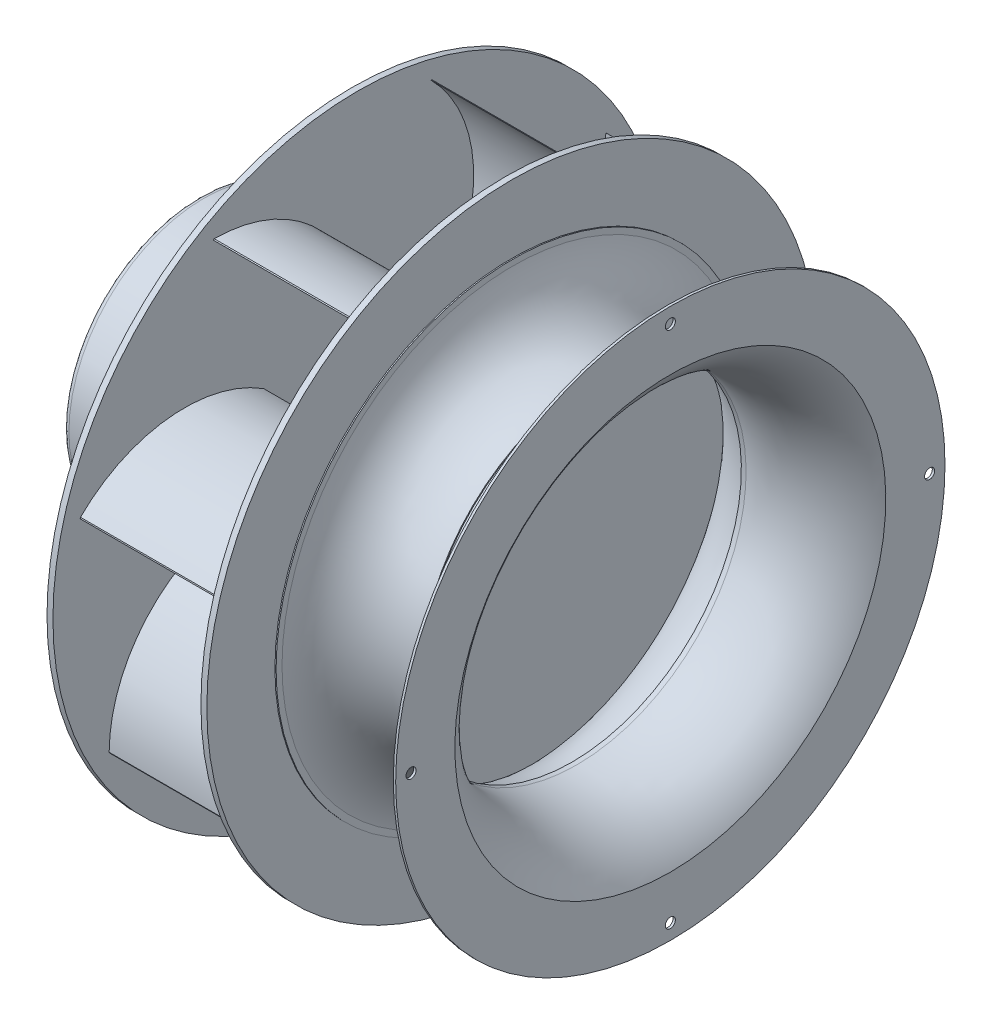
SolidWorks part; units mm, degrees
ref_plane "Front Plane" through (0, 0, 0) normal (0, 0, 1) x (1, 0, 0)
ref_plane "Top Plane" through (0, 0, 0) normal (0, 1, 0) x (1, 0, 0)
ref_plane "Right Plane" through (0, 0, 0) normal (1, 0, 0) x (0, 0, -1)
sketch "Sketch1" plane through (0, 0, 0) normal (0, 0, 1) x (1, 0, 0)
  line L0 (0, 0) -> (831.9083, 0) construction
  line L1 (0, 0) -> (0, 109)
  line L2 (5, 114) -> (70, 114)
  line L3 (70, 114) -> (70, 138)
  line L4 (70, 138) -> (90, 138)
  line L5 (90, 138) -> (90, 98)
  line L6 (90, 98) -> (95, 98)
  line L7 (95, 98) -> (95, 133)
  line L8 (95, 133) -> (105, 133)
  line L9 (105, 133) -> (105, 98)
  line L10 (105, 98) -> (130, 98)
  line L11 (130, 98) -> (130, 0)
  line L12 (130, 0) -> (0, 0)
  arc A0 (5, 114) -> (0, 109) centre (5, 109) ccw
  point P16 (0, 114)
  dimension "D10" = 5
  dimension "D1" = 114
  dimension "D2" = 24
  dimension "D3" = 70
  dimension "D4" = 40
  dimension "D5" = 35
  dimension "D6" = 5
  dimension "D7" = 20
  dimension "D8" = 10
  dimension "D9" = 60
revolve "Revolve1" add sketch "Sketch1" angle 360 about L0
sketch "Sketch2" plane through (130, 0, 0) normal (1, 0, 0) x (0, 0, -1)
  circle A0 centre (0, 0) radius 257.5
  dimension "D1" = 515
extrude "Extrude1" add sketch "Sketch2" along normal blind 5
sketch "Sketch9" plane through (130, 0, 0) normal (-1, 0, 0) x (0, 0, 1)
  circle A0 centre (0, 0) radius 252.5
  circle A1 centre (0, 0) radius 100
  circle A2 centre (0, 0) radius 257.5 construction
  dimension "D1" = 5
  dimension "D2" = 200
extrude "Extrude7" cut sketch "Sketch9" against normal blind 3
ref_plane "Plane1" through (260, 0, 0) normal (1, 0, 0) x (0, 0, -1)
sketch "Sketch3" plane through (260, 0, 0) normal (1, 0, 0) x (0, 0, -1)
  circle A0 centre (0, 0) radius 257.5
  dimension "D1" = 515
extrude "Extrude2" add sketch "Sketch3" along normal blind 5 separate body
sketch "Sketch4" plane through (135, 0, 0) normal (1, 0, 0) x (0, 0, -1)
  line L0 (0, 0) -> (0, 242.5) construction
  line L1 (0, 0) -> (128.75, 223.0015) construction
  line L2 (0, 112.5) -> (0.866, 112) construction
  line L3 (121.25, 210.0112) -> (122.116, 209.5112) construction
  line L4 (-121.25, 210.0112) -> (-122.116, 209.5112)
  line L5 (0, 112.5) -> (-0.866, 112)
  circle A0 centre (0, 0) radius 242.5 construction
  circle A1 centre (0, 0) radius 257.5 construction
  circle A2 centre (0, 0) radius 112.5 construction
  arc A3 (0, 112.5) -> (121.25, 210.0112) centre (121.9404, 85.0131) cw construction
  arc A4 (0.866, 112) -> (122.116, 209.5112) centre (122.8065, 84.5131) cw construction
  arc A5 (0, 112.5) -> (-121.25, 210.0112) centre (-121.9404, 85.0131) ccw
  arc A6 (-0.866, 112) -> (-122.116, 209.5112) centre (-122.8065, 84.5131) ccw
  dimension "D1" = 15
  dimension "D2" = 225
  dimension "D6" = 125
  dimension "D7" = 125
  dimension "D3" = 30
  dimension "D4" = 60
  dimension "D5" = 1
extrude "Extrude3" add sketch "Sketch4" along normal up to surface (130 mm away) up to face at (265, 0, -257.5)
ref_axis "Axis1" through (253.5503, 0, 0) along (-1, 0, 0)
pattern_circular "CirPattern1" count 8 over 360 about axis through (253.5503, 0, 0) along (-1, 0, 0) of "Extrude3"
sketch "Sketch5" plane through (0, 0, 0) normal (0, 0, 1) x (1, 0, 0)
  line L0 (0, 0) -> (527.2916, 0) construction
  line L1 (253.5503, 0) -> (75.411, 0) construction
  line L2 (265, 200) -> (266, 200)
  line L3 (266, 200) -> (266, 195)
  line L4 (265, 200) -> (265, 195)
  line L5 (334, 146) -> (334, 145)
  line L6 (70, 138) -> (70, -138) construction
  line L7 (265, -257.5) -> (265, 257.5) construction
  arc A0 (266, 195) -> (334, 146) centre (325.1029, 205.3367) ccw
  arc A1 (265, 195) -> (334, 145) centre (324.2891, 204.2089) ccw
  dimension "D7" = 60
  dimension "D8" = 60
  dimension "D1" = 145
  dimension "D2" = 1
  dimension "D3" = 1
  dimension "D4" = 5
  dimension "D5" = 200
  dimension "D6" = 264
revolve "Revolve2" add sketch "Sketch5" angle 360 about L0
ref_plane "Plane3" through (399, 0, 0) normal (1, 0, 0) x (0, 0, -1)
sketch "Sketch6" plane through (0, 0, 0) normal (0, 0, 1) x (1, 0, 0)
  line L0 (399, 232) -> (397, 232)
  line L1 (399, -251.35) -> (399, 251.35) construction
  line L2 (397, 232) -> (397, 182)
  line L3 (0, 0) -> (615.1417, 0) construction
  line L4 (0, 114) -> (0, -114) construction
  line L5 (253.5503, 0) -> (75.411, 0) construction
  line L6 (399, 232) -> (399, 182)
  line L7 (316, 145) -> (320, 145)
  line L8 (316, 145) -> (316, 143)
  line L9 (316, 143) -> (320, 143)
  arc A0 (320, 145) -> (397, 182) centre (329.2033, 224.4689) ccw
  arc A1 (320, 143) -> (399, 182) centre (329.9389, 222.3802) ccw
  dimension "D7" = 80
  dimension "D8" = 80
  dimension "D1" = 232
  dimension "D2" = 2
  dimension "D3" = 182
  dimension "D4" = 83
  dimension "D5" = 145
  dimension "D6" = 4
revolve "Revolve3" add sketch "Sketch6" angle 360 about L3
sketch "Sketch7" plane through (399, 0, 0) normal (1, 0, 0) x (0, 0, -1)
  line L0 (0, 0) -> (0, 219) construction
  circle A0 centre (0, 0) radius 219 construction
  circle A1 centre (0, 219) radius 4.25
  dimension "D1" = 438
  dimension "D2" = 8.5
extrude "Extrude5" cut sketch "Sketch7" against normal blind 5
pattern_circular "CirPattern2" count 4 over 360 about axis through (253.5503, 0, 0) along (-1, 0, 0) of "Extrude5"
sketch "Sketch8" plane through (0, 0, 0) normal (1, 0, 0) x (0, 0, -1)
  line L0 (0, 0) -> (0, 126) construction
  circle A0 centre (0, 0) radius 126 construction
  circle A1 centre (0, 126) radius 5
  dimension "D1" = 252
  dimension "D2" = 10
extrude "Extrude6" cut sketch "Sketch8" along normal up to surface (90 mm away) up to face at (90, 0, 138)
pattern_circular "CirPattern3" count 8 over 360 about axis through (253.5503, 0, 0) along (-1, 0, 0) of "Extrude6"
